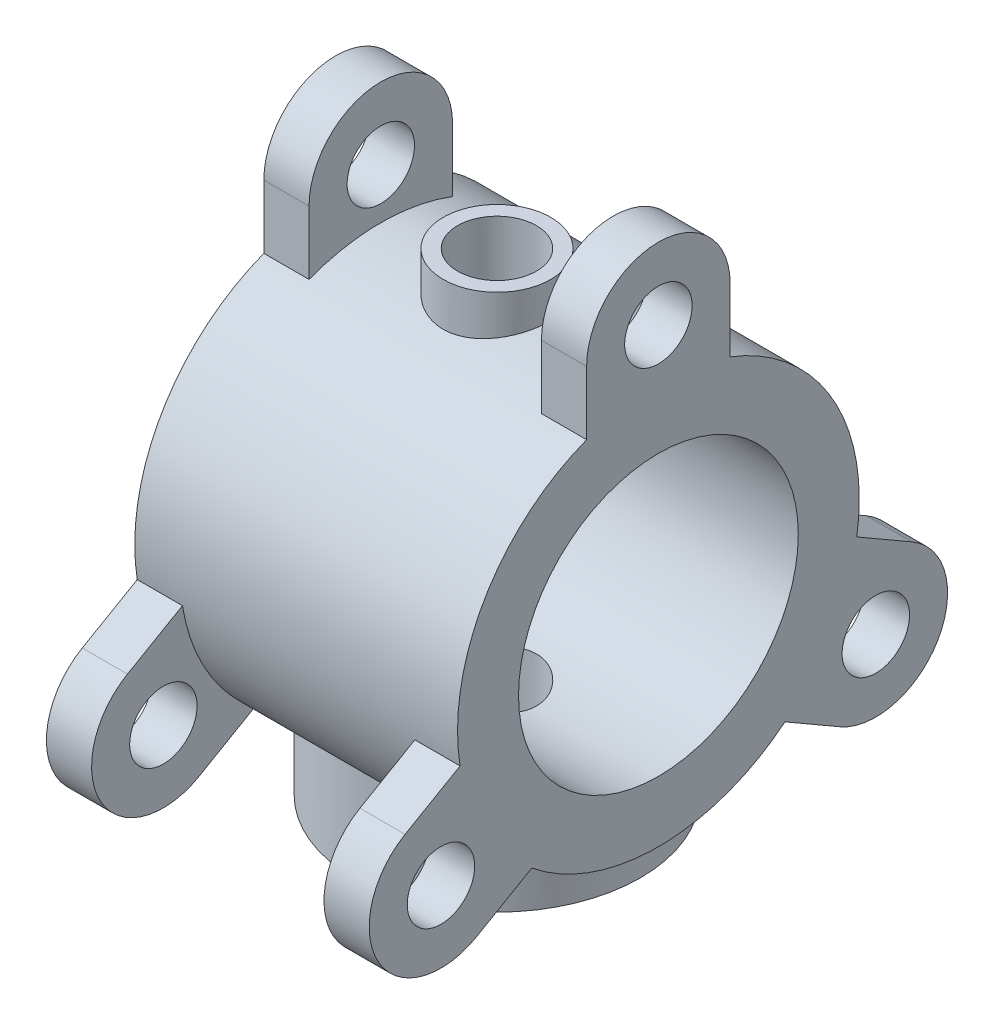
SolidWorks part; units mm, degrees
ref_plane "Front Plane" through (0, 0, 0) normal (0, 0, 1) x (1, 0, 0)
ref_plane "Top Plane" through (0, 0, 0) normal (0, 1, 0) x (1, 0, 0)
ref_plane "Right Plane" through (0, 0, 0) normal (1, 0, 0) x (0, 0, -1)
sketch "Sketch1" plane through (0, 0, 0) normal (1, 0, 0) x (0, 0, -1)
  circle A0 centre (0, 0) radius 28
  circle A1 centre (0, 0) radius 19.5
  dimension "D1" = 56
  dimension "D2" = 39
extrude "Boss-Extrude1" add sketch "Sketch1" along normal mid plane 45
ref_plane "Plane1" through (0, 33, 0) normal (0, 1, 0) x (1, 0, 0)
sketch "Sketch2" plane through (0, 33, 0) normal (0, 1, 0) x (1, 0, 0)
  circle A0 centre (0, 0) radius 7.5
  dimension "D1" = 15
extrude "Boss-Extrude2" add sketch "Sketch2" against normal up to next
ref_plane "Plane2" through (0, -33, 0) normal (0, 1, 0) x (1, 0, 0)
sketch "Sketch3" plane through (0, -33, 0) normal (0, 1, 0) x (1, 0, 0)
  circle A0 centre (0, 0) radius 20
  dimension "D1" = 40
extrude "Boss-Extrude3" add sketch "Sketch3" along normal up to next
hole_wizard "Hole1" positions "Sketch4" profile "Sketch5" legacy end condition through all
sketch "Sketch4" plane through (0, -33, 0) normal (0, -1, 0) x (-1, 0, 0)
  point P0 (0, 0)
sketch "Sketch5" plane through (0, -33, 0) normal (1, 0, 0) x (0, 0, -1)
  line L0 (0, 0) -> (0, 66)
  line L1 (0, 66) -> (5.5, 66)
  line L2 (5.5, 66) -> (5.5, 5)
  line L3 (5.5, 5) -> (10, 5)
  line L4 (10, 5) -> (10, 0)
  line L5 (10, 0) -> (0, 0)
  line L6 (0, 110) -> (0, -10) construction
  dimension "Diameter" = 11
  dimension "Depth" = 66
  dimension "C-Bore Diameter" = 20
  dimension "C-Bore Depth" = 5
sketch "Sketch6" plane through (-22.5, 0, 0) normal (-1, 0, 0) x (0, 0, 1)
  line L0 (0, 0) -> (41.0441, 0) construction
  line L3 (0, 0) -> (0, -40.8414) construction
  line L6 (-10.004, 35) -> (-10.004, 16.7383)
  line L7 (10.004, 35) -> (10.004, 16.7383)
  circle A0 centre (0, 0) radius 35 construction
  arc A11 (-10.004, 35) -> (10.004, 35) centre (0, 35) cw
  arc A12 (-10.004, 16.7383) -> (10.004, 16.7383) centre (0, 0) cw
  circle A13 centre (0, 0) radius 19.5 construction
  point P3 (0, 0)
  point P6 (0, 33.8924)
  point P9 (0, 0)
  point P15 (-10.0039, 16.4138)
  dimension "D1" = 70
  dimension "D2" = 10.004
extrude "Boss-Extrude4" add sketch "Sketch6" against normal blind 6.3
pattern_circular "CirPattern2" count 3 over 360 about axis through (22.5, 0, 0) along (-1, 0, 0) of "Boss-Extrude4"
mirror "Mirror3" about plane through (0, 0, 0) normal (1, 0, 0) of "CirPattern2", "Boss-Extrude4"
hole_wizard "Hole4" positions "Sketch12" profile "Sketch13" legacy end condition up to next
sketch "Sketch12" plane through (-22.5, 0, 0) normal (-1, 0, 0) x (0, 0, 1)
  point P0 (30.3109, -17.5)
  point P3 (0, 35)
  point P6 (-30.3109, -17.5)
sketch "Sketch13" plane through (-22.5, -17.5, 30.3109) normal (0, 1, 0) x (0, 0, 1)
  line L0 (0, 0) -> (0, 6.3)
  line L1 (0, 6.3) -> (4.7, 6.3)
  line L2 (4.7, 6.3) -> (4.7, 0)
  line L3 (4.7, 0) -> (0, 0)
  line L4 (0, 110) -> (0, -10) construction
  dimension "Diameter" = 9.4
  dimension "Depth" = 6.3
hole_wizard "Hole5" positions "Sketch14" profile "Sketch15" legacy end condition up to next
sketch "Sketch14" plane through (22.5, 0, 0) normal (1, 0, 0) x (0, 0, -1)
  point P0 (0, 35)
  point P3 (30.3109, -17.5)
  point P6 (-30.3109, -17.5)
sketch "Sketch15" plane through (22.5, 35, 0) normal (0, 1, 0) x (0, 0, -1)
  line L0 (0, 0) -> (0, 6.3)
  line L1 (0, 6.3) -> (4.7, 6.3)
  line L2 (4.7, 6.3) -> (4.7, 0)
  line L3 (4.7, 0) -> (0, 0)
  line L4 (0, 110) -> (0, -10) construction
  dimension "Diameter" = 9.4
  dimension "Depth" = 6.3
